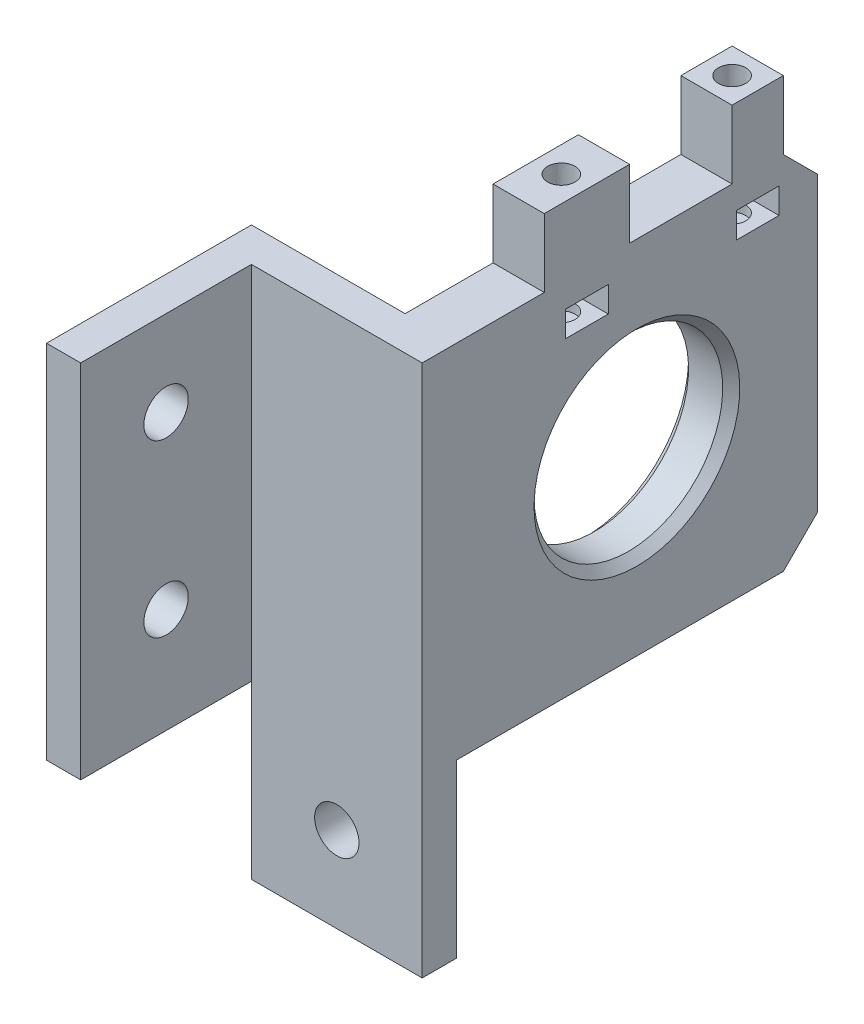
SolidWorks part; units mm, degrees
ref_plane "Přední rovina" through (0, 0, 0) normal (0, 0, 1) x (1, 0, 0)
ref_plane "Horní rovina" through (0, 0, 0) normal (0, 1, 0) x (1, 0, 0)
ref_plane "Pravá rovina" through (0, 0, 0) normal (1, 0, 0) x (0, 0, -1)
sketch "Skica2" plane through (0, 0, 0) normal (0, 0, 1) x (1, 0, 0)
  line L0 (-24.5243, -350) -> (-24.5243, 0) construction
  line L1 (-4.5243, -40) -> (-24.5243, -40)
  line L2 (-4.5243, -40) -> (-4.5243, -82.3)
  line L3 (-4.5243, -82.3) -> (-24.5243, -82.3)
  line L4 (-24.5243, -40) -> (-24.5243, -82.3)
  line L5 (-344.5243, -82.3) -> (-355.5243, -82.3) construction
extrude "Přidat vysunutím1" add sketch "Skica2" along normal blind 4
sketch "Skica3" plane through (-24.5243, 0, 0) normal (-1, 0, 0) x (0, 0, 1)
  line L0 (4, -82.3) -> (0, -82.3) construction
  line L1 (4, -40) -> (-20, -40)
  line L2 (4, -40) -> (4, -82.3)
  line L3 (4, -82.3) -> (-20, -82.3)
  line L4 (-20, -40) -> (-20, -82.3)
  line L5 (-20, -350) -> (-20, 0) construction
extrude "Přidat vysunutím2" add sketch "Skica3" along normal blind 4
sketch "Skica4" plane through (0, 0, 4) normal (0, 0, 1) x (1, 0, 0)
  line L0 (-28.5243, -82.3) -> (-4.5243, -82.3) construction
  line L1 (-10.5243, -40) -> (-4.5243, -40)
  line L2 (-10.5243, -40) -> (-10.5243, -82.3)
  line L3 (-10.5243, -82.3) -> (-4.5243, -82.3)
  line L4 (-4.5243, -40) -> (-4.5243, -82.3)
  line L5 (-4.5243, -82.3) -> (-4.5243, -40) construction
  dimension "D1" = 6
extrude "Přidat vysunutím3" add sketch "Skica4" along normal up to surface (42.3 mm away)
sketch "Skica5" plane through (-4.5243, 0, 0) normal (1, 0, 0) x (0, 0, -1)
  circle A0 centre (-25.15, -61.15) radius 11.05
  dimension "D1" = 22.1
extrude "Odebrat vysunutím1" cut sketch "Skica5" against normal blind 7
sketch "Skica7" plane through (-28.5243, 0, 0) normal (-1, 0, 0) x (0, 0, 1)
  line L0 (-20, -40) -> (-20, -82.3) construction
  line L1 (4, -40) -> (-20, -40) construction
  circle A0 centre (-10, -50) radius 2.6
  circle A1 centre (-10, -70) radius 2.6
  dimension "D3" = 5.2
  dimension "D1" = 10
  dimension "D2" = 10
  dimension "D4" = 2
extrude "Odebrat vysunutím3" cut sketch "Skica7" against normal blind 4
chamfer "Zkosení1" distance 1 angle 45 1 edges at (-10.5243, -50.1, 25.15)
sketch "Skica8" plane through (0, -82.3, 0) normal (0, -1, 0) x (1, 0, 0)
  line L0 (-28.5243, 4) -> (-10.5243, 4) construction
  line L1 (-4.5243, 0) -> (-24.5243, 0)
  line L2 (-4.5243, 0) -> (-4.5243, 4)
  line L3 (-4.5243, 4) -> (-24.5243, 4)
  line L4 (-24.5243, 0) -> (-24.5243, 4)
extrude "Přidat vysunutím4" add sketch "Skica8" along normal up to surface (20.0916 mm away)
sketch "Skica9" plane through (0, 0, 4) normal (0, 0, 1) x (1, 0, 0)
  line L0 (-24.5243, -102.3916) -> (-4.5243, -102.3916) construction
  line L1 (-4.5243, -102.3916) -> (-4.5243, -82.3) construction
  circle A0 centre (-14.5243, -92.3916) radius 2.6
  dimension "D3" = 5.2
  dimension "D1" = 10
  dimension "D2" = 10
extrude "Odebrat vysunutím4" cut sketch "Skica9" against normal blind 4
sketch "Skica10" plane through (-10.5243, 0, 0) normal (-1, 0, 0) x (0, 0, 1)
  line L0 (46.3, -44) -> (42.3, -40)
  line L1 (46.3, -40) -> (46.3, -82.3) construction
  line L2 (42.3, -40) -> (46.3, -44) construction
  line L3 (46.3, -40) -> (4, -40) construction
  line L4 (42.3, -40) -> (46.5659, -39.2593)
  line L5 (46.5659, -39.2593) -> (46.3, -44)
  line L6 (42.3, -82.3) -> (46.3, -78.3)
  line L7 (46.3, -82.3) -> (4, -82.3) construction
  line L8 (46.3, -78.3) -> (42.3, -82.3) construction
  line L9 (46.3, -78.3) -> (47.7456, -80.3)
  line L10 (47.7456, -80.3) -> (46.3, -85.4154)
  line L11 (46.3, -85.4154) -> (42.3, -82.3)
extrude "Odebrat vysunutím5" cut sketch "Skica10" against normal blind 80
mirror "Zrcadlit1" about plane through (-28.5243, -40, -20) normal (0, 0, 1) of bodies 109
sketch "Skica11" plane through (-28.5243, 0, 0) normal (-1, 0, 0) x (0, 0, 1)
  line L1 (-20, -40) -> (64.6922, -40)
  line L2 (-20, -40) -> (-20, -120.4742)
  line L3 (-20, -120.4742) -> (64.6922, -120.4742)
  line L4 (64.6922, -40) -> (64.6922, -120.4742)
extrude "Odebrat vysunutím6" cut sketch "Skica11" against normal up to surface (24 mm away) up to face at (-4.5243, -61.15, 14.1)
sketch "Skica12" plane through (0, -40, 0) normal (0, 1, 0) x (1, 0, 0)
  line L0 (-10.5243, 82.3) -> (-10.5243, 44) construction
  line L1 (-4.5243, 82.3) -> (-10.5243, 82.3)
  line L2 (-4.5243, 82.3) -> (-4.5243, 76.3)
  line L3 (-4.5243, 76.3) -> (-10.5243, 76.3)
  line L4 (-10.5243, 82.3) -> (-10.5243, 76.3)
  line L5 (-4.5243, 82.3) -> (-4.5243, 40) construction
  line L6 (-4.5243, 64.3) -> (-10.5243, 64.3)
  line L7 (-4.5243, 64.3) -> (-4.5243, 54.3)
  line L8 (-4.5243, 54.3) -> (-10.5243, 54.3)
  line L9 (-10.5243, 64.3) -> (-10.5243, 54.3)
  line L10 (-384.5243, 76.3) -> (-4.5243, 76.3) construction
  line L11 (-384.5243, 64.3) -> (-4.5243, 64.3) construction
  dimension "D1" = 10
extrude "Přidat vysunutím5" add sketch "Skica12" along normal blind 8
sketch "Skica13" plane through (0, -32, 0) normal (0, 1, 0) x (1, 0, 0)
  line L0 (-4.5243, 54.3) -> (-4.5243, 64.3) construction
  line L1 (-4.5243, 76.3) -> (-4.5243, 82.3) construction
  circle A0 centre (-7.5243, 59.3) radius 1.6
  circle A1 centre (-7.5243, 79.3) radius 1.6
  point P0 (-4.5243, 59.3)
  point P1 (-4.5243, 79.3)
  dimension "D1" = 3.2
extrude "Odebrat vysunutím7" cut sketch "Skica13" against normal blind 15
sketch "Skica14" plane through (-4.5243, 0, 0) normal (1, 0, 0) x (0, 0, -1)
  line L0 (338.2, -44.439) -> (47.5573, -44.439) construction
  line L1 (338.2, -42.939) -> (338.2, -45.939) construction
  line L2 (59.3, -32) -> (59.3, -44.439) construction
  line L3 (61.8, -42.939) -> (56.8, -42.939)
  line L4 (61.8, -42.939) -> (61.8, -45.939)
  line L5 (61.8, -45.939) -> (56.8, -45.939)
  line L6 (56.8, -42.939) -> (56.8, -45.939)
  line L7 (61.8, -42.939) -> (56.8, -45.939) construction
  line L8 (61.8, -45.939) -> (56.8, -42.939) construction
  line L9 (54.3, -32) -> (64.3, -32) construction
  line L10 (79.3, -32) -> (79.3, -44.439) construction
  line L11 (76.3, -32) -> (82.3, -32) construction
  line L13 (81.8, -45.939) -> (76.8, -45.939)
  line L14 (81.8, -45.939) -> (81.8, -42.939)
  line L15 (81.8, -42.939) -> (76.8, -42.939)
  line L16 (76.8, -45.939) -> (76.8, -42.939)
  line L17 (81.8, -45.939) -> (76.8, -42.939) construction
  line L18 (81.8, -42.939) -> (76.8, -45.939) construction
  point P4 (59.3, -44.439)
  dimension "D1" = 5
  dimension "D2" = 3
extrude "Odebrat vysunutím8" cut sketch "Skica14" against normal blind 15
chamfer "Zkosení2" distance 1 angle 45 1 edges at (-4.5243, -61.15, -54.1)
